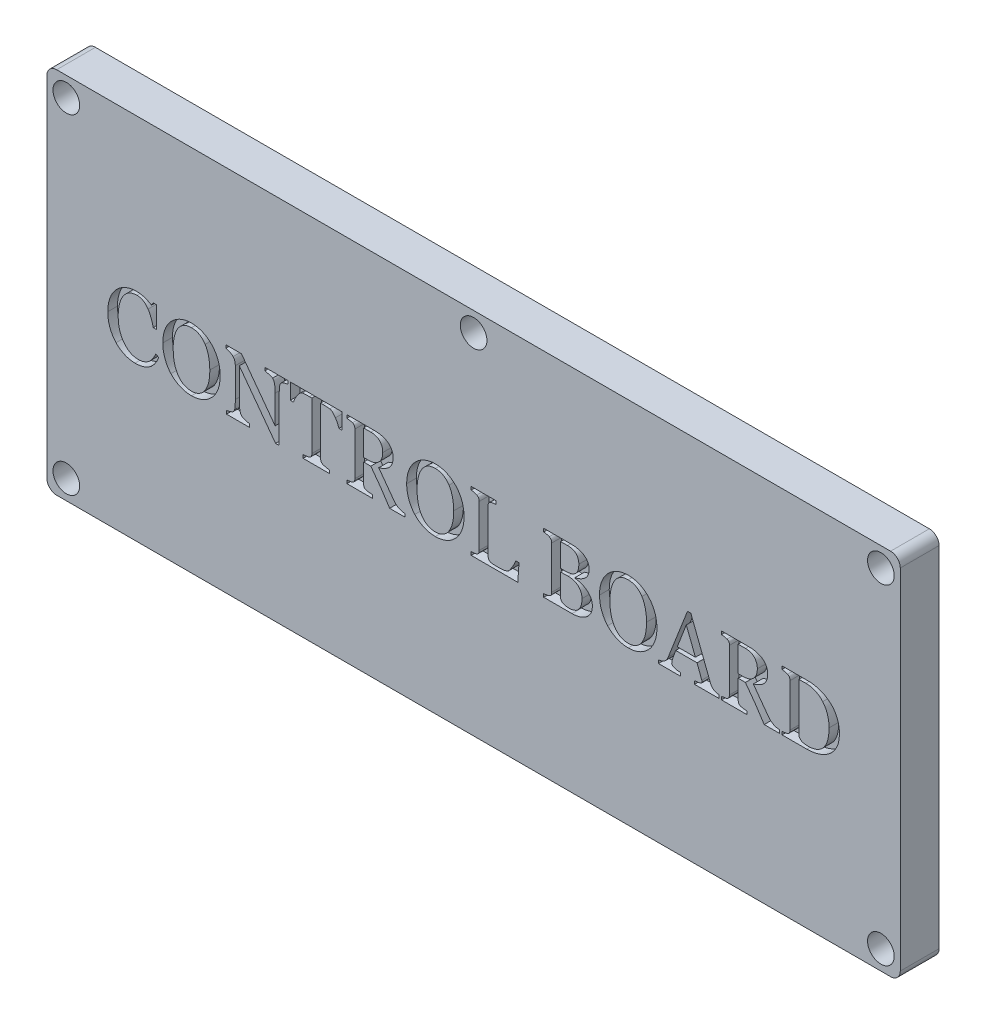
SolidWorks part; units mm, degrees
ref_plane "前视基准面" through (0, 0, 0) normal (0, 0, 1) x (1, 0, 0)
ref_plane "上视基准面" through (0, 0, 0) normal (0, 1, 0) x (1, 0, 0)
ref_plane "右视基准面" through (0, 0, 0) normal (1, 0, 0) x (0, 0, -1)
other "Configuration Table"
sketch "草图1" plane through (0, 0, 0) normal (0, 0, 1) x (1, 0, 0)
  line L1 (88, -38) -> (-88, -38)
  line L2 (88, -38) -> (88, 38)
  line L3 (88, 38) -> (-88, 38)
  line L4 (-88, -38) -> (-88, 38)
  line L5 (88, -38) -> (-88, 38) construction
  line L6 (88, 38) -> (-88, -38) construction
  point P0 (0, 0)
  dimension "D1" = 176
  dimension "D2" = 76
extrude "凸台-拉伸1" add sketch "草图1" along normal blind 8
sketch "草图2" plane through (0, 0, 0) normal (0, 0, -1) x (-1, 0, 0)
  line L0 (-88, -38) -> (-88, 38) construction
  line L1 (-88, 38) -> (88, 38) construction
  line L2 (88, -38) -> (-88, -38) construction
  line L3 (88, 38) -> (88, -38) construction
  circle A0 centre (-84, 34) radius 1.6
  circle A1 centre (-84, -34) radius 1.6
  circle A2 centre (-84, 0) radius 2.6
  circle A3 centre (0, 34) radius 1.6
  circle A4 centre (84, 34) radius 1.6
  circle A5 centre (84, 0) radius 2.6
  circle A6 centre (84, -34) radius 1.6
  circle A7 centre (0, -34) radius 2.6
  point P20 (0, 0)
  point P23 (0, 0)
  point P24 (0, 0)
  point P27 (0, 0)
  point P28 (0, 38)
  point P29 (-88, 0)
  dimension "D1" = 3.2
  dimension "D2" = 5.2
  dimension "D3" = 3.2
  dimension "D4" = 3.2
  dimension "D5" = 3.2
  dimension "D6" = 5.2
  dimension "D7" = 5.2
  dimension "D8" = 3.2
  dimension "D9" = 4
  dimension "D10" = 4
  dimension "D11" = 4
  dimension "D12" = 4
extrude "切除-拉伸1" cut sketch "草图2" against normal through all contours A0 | A3 | A4 | A1 | A6 region at (84, 34, 0) region at (0, 34, 0) region at (-84, 34, 0)
extrude "切除-拉伸2" cut sketch "草图2<3>" against normal blind 3 contours A2 | A7 | A5
sketch "草图2<3>" plane through (0, 0, 0) normal (0, 0, -1) x (-1, 0, 0) same geometry as "草图2"
sketch "草图4" plane through (0, 0, 8) normal (0, 0, 1) x (1, 0, 0)
  circle A0 centre (-84, 34) radius 2.75
  circle A1 centre (0, 34) radius 2.75
  circle A2 centre (-84, -34) radius 2.75
  circle A3 centre (84, 34) radius 2.75
  circle A4 centre (84, -34) radius 2.75
  dimension "D1" = 5.5
extrude "切除-拉伸3" cut sketch "草图4" against normal blind 4
fillet "圆角1" radius 2 4 edges at (88, 38, 4) (88, -38, 4) (-88, -38, 4) (-88, 38, 4)
sketch "草图5" plane through (0, 0, 8) normal (0, 0, 1) x (1, 0, 0)
  line L0 (-88, -6) -> (88, -6) construction
  line L1 (-88, 36) -> (-88, -36) construction
  line L2 (88, -36) -> (88, 36) construction
  line L3 (-86, -38) -> (86, -38) construction
  text T0 "CONTROL BOARD" font "Georgia" height in points 48
  dimension "D1" = 32
extrude "切除-拉伸4" cut sketch "草图5" against normal blind 2
